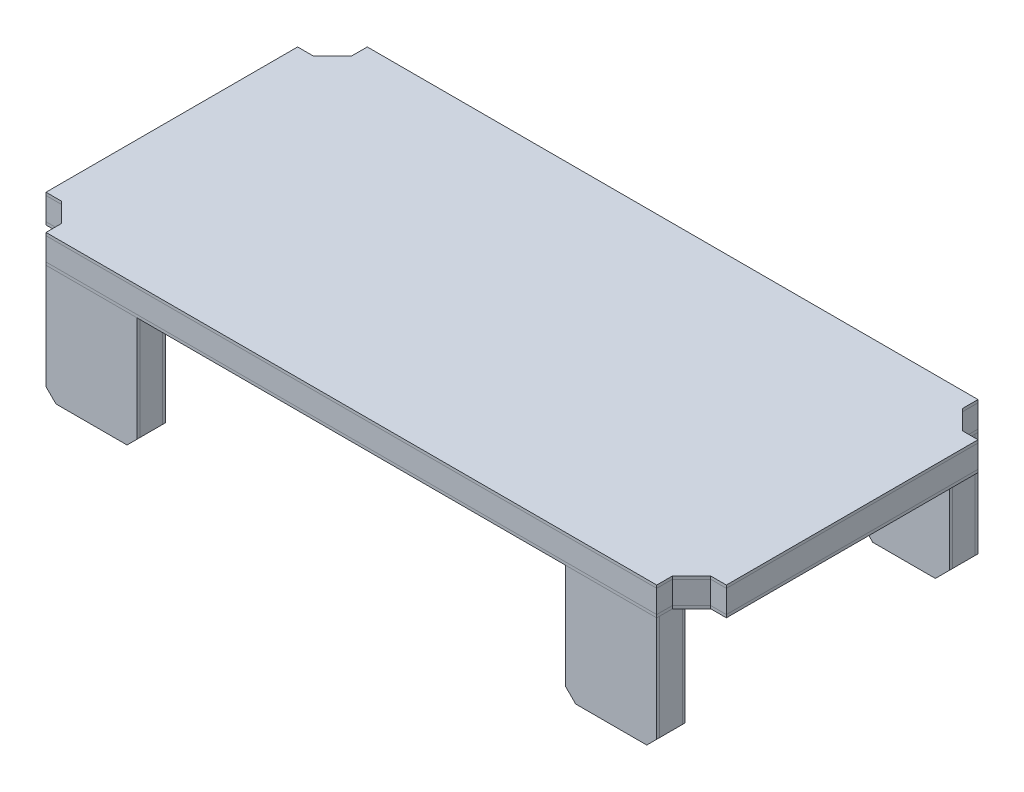
SolidWorks part; units mm, degrees
ref_plane "Front Plane" through (0, 0, 0) normal (0, 0, 1) x (1, 0, 0)
ref_plane "Top Plane" through (0, 0, 0) normal (0, 1, 0) x (1, 0, 0)
ref_plane "Right Plane" through (0, 0, 0) normal (1, 0, 0) x (0, 0, -1)
sketch "Sketch2" plane through (0, 0, 0) normal (0, 1, 0) x (1, 0, 0)
  line L0 (-104.65, 50) -> (-104.65, 41.5) construction
  line L1 (-113.15, -50) -> (113.15, -50) construction
  line L2 (-113.15, -50) -> (-113.15, 50) construction
  line L3 (-113.15, 50) -> (113.15, 50) construction
  line L4 (113.15, -50) -> (113.15, 50) construction
  line L5 (-113.15, -50) -> (113.15, 50) construction
  line L6 (-113.15, 50) -> (113.15, -50) construction
  line L7 (-110.4, 51) -> (-107.4, 51) construction
  line L8 (-110.4, 51) -> (-110.4, 57) construction
  line L9 (-110.4, 57) -> (-107.4, 57)
  line L10 (-107.4, 51) -> (-107.4, 57)
  line L11 (-114.15, 47.25) -> (-120.15, 47.25) construction
  line L12 (-114.15, 47.25) -> (-114.15, 44.25) construction
  line L13 (-114.15, 44.25) -> (-120.15, 44.25)
  line L14 (-120.15, 47.25) -> (-120.15, 44.25)
  line L15 (-104.65, 41.5) -> (-113.15, 41.5) construction
  line L16 (-108.9, 41.5) -> (-108.9, 51) construction
  line L17 (-104.65, 45.75) -> (-114.15, 45.75) construction
  line L18 (-110.4, 51) -> (-110.4, 50) construction
  line L19 (-110.4, 50) -> (-113.15, 47.25) construction
  line L20 (-113.15, 47.25) -> (-114.15, 47.25) construction
  line L21 (-114.15, 44.25) -> (-107.4, 51)
  line L22 (-110.4, 57) -> (-120.15, 57)
  line L23 (-120.15, 57) -> (-120.15, 47.25)
  point P0 (0, 0)
  dimension "D1" = 226.3
  dimension "D2" = 100
  dimension "D3" = 8.5
  dimension "D4" = 1
  dimension "D5" = 3
  dimension "D6" = 6
sketch "Sketch3" plane through (0, 0, 0) normal (0, 1, 0) x (1, 0, 0)
  line L0 (-113.15, -50) -> (113.15, 50) construction
  line L1 (119.65, -56.5) -> (-119.65, -56.5)
  line L2 (119.65, -56.5) -> (119.65, 56.5)
  line L3 (119.65, 56.5) -> (-119.65, 56.5)
  line L4 (-119.65, -56.5) -> (-119.65, 56.5)
  line L5 (119.65, -56.5) -> (-119.65, 56.5) construction
  line L6 (119.65, 56.5) -> (-119.65, -56.5) construction
  line L7 (-110.4, 57) -> (-107.4, 57) construction
  line L8 (-120.15, 47.25) -> (-120.15, 44.25) construction
  point P0 (0, 0)
  dimension "D1" = 0.5
  dimension "D2" = 0.5
extrude "Boss-Extrude1" add sketch "Sketch3" along normal blind 1 from offset 4
mirror "Mirror3" about plane through (0, 0, 0) normal (0, 1, 0) of bodies 125
extrude "Boss-Extrude2" add sketch "Sketch3<2>" along normal up to surface (4 mm away) and the other way up to surface (4 mm away) separate body up to face at (0, 4, 0) other way up to face at (0, -4, 0)
sketch "Sketch3<2>" plane through (0, 0, 0) normal (0, 1, 0) x (1, 0, 0) same geometry as "Sketch3"
extrude "Cut-Extrude1" cut sketch "Sketch2" against normal through all both and the other way through all
mirror "Mirror5" about plane through (0, 0, 0) normal (0, 0, 1) of "Cut-Extrude1"
mirror "Mirror6" about plane through (0, 0, 0) normal (1, 0, 0) of "Mirror5", "Cut-Extrude1"
sketch "Sketch4" plane through (0, -5, 0) normal (0, -1, 0) x (1, 0, 0)
  line L1 (-107.4, 56.5) -> (-75.4, 56.5)
  line L2 (-107.4, 56.5) -> (-107.4, 55.5)
  line L3 (-107.4, 55.5) -> (-75.4, 55.5)
  line L4 (-75.4, 56.5) -> (-75.4, 55.5)
  dimension "D1" = 32
  dimension "D2" = 1
extrude "Boss-Extrude3" add sketch "Sketch4" along normal blind 42 separate body
chamfer "Chamfer1" distance 5 angle 45 2 edges at (-75.4, -47, 56) (-107.4, -47, 56)
sketch "Sketch6" plane through (0, 0, 55.5) normal (0, 0, -1) x (-1, 0, 0)
  line L4 (107.4, -5) -> (75.4, -5)
  line L5 (75.4, -5) -> (75.4, -42)
  line L6 (80.4, -47) -> (102.4, -47)
  line L7 (107.4, -42) -> (107.4, -5)
  line L8 (107.4, -5) -> (75.4, -5)
  line L9 (75.4, -5) -> (75.4, -42)
  line L10 (80.4, -47) -> (102.4, -47)
  line L11 (107.4, -42) -> (107.4, -5)
  line L14 (75.4, -42) -> (80.4, -47)
  line L15 (75.4, -42) -> (80.4, -47)
  line L16 (102.4, -47) -> (107.4, -42)
  line L17 (102.4, -47) -> (107.4, -42)
  dimension "D1" = 0
extrude "Boss-Extrude4" add sketch "Sketch6" along normal blind 8 separate body
sketch "Sketch7" plane through (0, 0, 47.5) normal (0, 0, -1) x (-1, 0, 0)
  line L4 (107.4, -42) -> (107.4, -5)
  line L5 (107.4, -5) -> (75.4, -5)
  line L6 (75.4, -5) -> (75.4, -42)
  line L7 (80.4, -47) -> (102.4, -47)
  line L8 (107.4, -42) -> (107.4, -5)
  line L9 (107.4, -5) -> (75.4, -5)
  line L10 (75.4, -5) -> (75.4, -42)
  line L11 (80.4, -47) -> (102.4, -47)
  line L14 (75.4, -42) -> (80.4, -47)
  line L15 (75.4, -42) -> (80.4, -47)
  line L16 (102.4, -47) -> (107.4, -42)
  line L17 (102.4, -47) -> (107.4, -42)
  dimension "D1" = 0
extrude "Boss-Extrude5" add sketch "Sketch7" along normal blind 1 separate body
chamfer "Chamfer2" distance 1.5 angle 45 1 edges at (-91.4, -47, 56.5)
chamfer "Chamfer3" distance 0.5 angle 45 1 edges at (-91.4, -47, 55.5)
mirror "Mirror7" about plane through (0, 0, 0) normal (0, 0, 1) of bodies 143 142 141
mirror "Mirror8" about plane through (0, 0, 0) normal (1, 0, 0) of bodies 146 145 143 142 144 141
